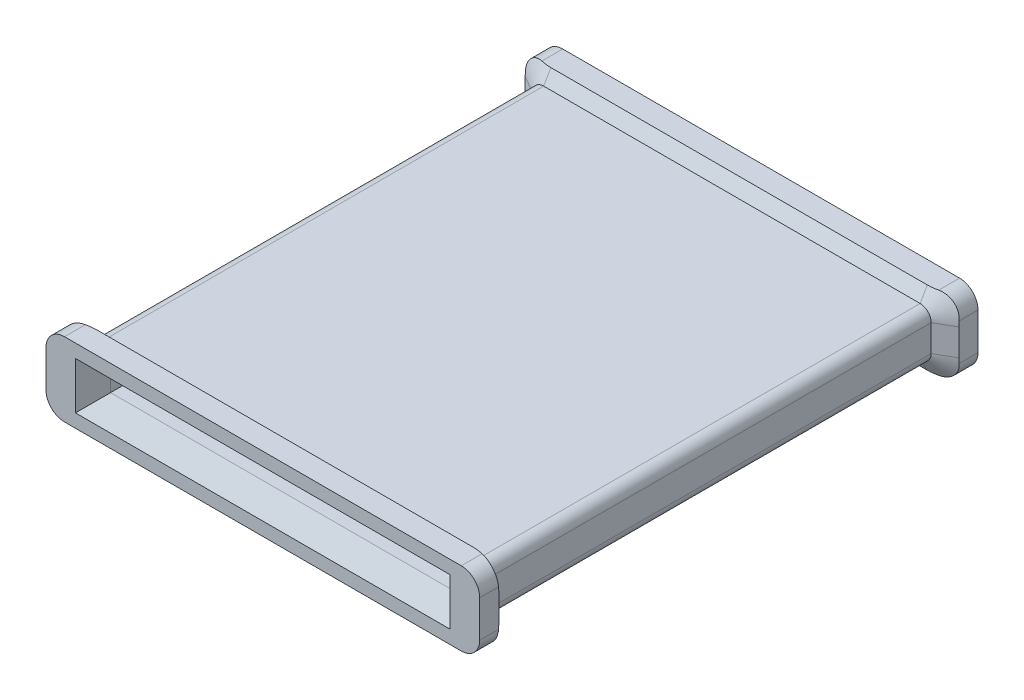
SolidWorks part; units mm, degrees
material "ABS"
ref_plane "Front Plane" through (0, 0, 0) normal (0, 0, 1) x (1, 0, 0)
ref_plane "Top Plane" through (0, 0, 0) normal (0, 1, 0) x (1, 0, 0)
ref_plane "Right Plane" through (0, 0, 0) normal (1, 0, 0) x (0, 0, -1)
sketch "Sketch1" plane through (0, 0, 0) normal (0, 0, 1) x (1, 0, 0)
  line L0 (0, 8) -> (47, 8)
  line L3 (47, 8) -> (47, 0)
  line L4 (47, 0) -> (0, 0)
  line L5 (0, 0) -> (0, 8)
  line L9 (3.5, 6.25) -> (43.5, 6.25)
  line L10 (3.5, 6.25) -> (3.5, 1.75)
  line L11 (3.5, 1.75) -> (43.5, 1.75)
  line L12 (43.5, 6.25) -> (43.5, 1.75)
  dimension "D1" = 1.75
  dimension "D2" = 40
  dimension "D4" = 4.5
  dimension "D5" = 1.75
  dimension "D7" = 3.5
  dimension "D8" = 3.5
extrude "Boss-Extrude1" add sketch "Sketch1" along normal blind 54
sketch "Sketch2" plane through (0, 0, 54) normal (0, 0, 1) x (1, 0, 0)
  line L1 (3.1, 6.65) -> (43.9, 6.65)
  line L2 (1.9, 5.45) -> (1.9, 2.55)
  line L3 (3.1, 1.35) -> (43.9, 1.35)
  line L4 (45.1, 5.45) -> (45.1, 2.55)
  line L5 (3.5, 1.75) -> (43.5, 1.75) construction
  line L6 (43.5, 6.25) -> (3.5, 6.25) construction
  line L8 (3.5, 6.25) -> (3.5, 1.75) construction
  line L9 (43.5, 1.75) -> (43.5, 6.25) construction
  arc A0 (1.9, 2.55) -> (3.1, 1.35) centre (3.1, 2.55) ccw
  arc A1 (43.9, 1.35) -> (45.1, 2.55) centre (43.9, 2.55) ccw
  arc A2 (43.9, 6.65) -> (45.1, 5.45) centre (43.9, 5.45) cw
  arc A3 (3.1, 6.65) -> (1.9, 5.45) centre (3.1, 5.45) ccw
  dimension "D1" = 1.2
  dimension "D2" = 0.4
  dimension "D3" = 1.6
  dimension "D4" = 1.6
  dimension "D5" = 0.4
extrude "Cut-Extrude1" cut sketch "Sketch2" against normal offset from surface (50 mm away) 2 from offset 2 flip side to cut up to face at (23.5, 4, 0) offset against normal yes
fillet "Fillet1" radius 2 8 edges at (47, 8, 53) (47, 0, 53) (47, 0, 1) (47, 8, 1) (0, 0, 1) (0, 8, 1) (0, 0, 53) (0, 8, 53)
chamfer "Chamfer4" distance 1.17 angle 60 16 edges at (1.9, 4, 52) (2.2515, 1.7015, 52) (2.2515, 6.2985, 52) (23.5, 1.35, 52) (23.5, 6.65, 52) (44.7485, 1.7015, 52) (44.7485, 6.2985, 52) (45.1, 4, 52) (1.9, 4, 2) (2.2515, 1.7015, 2) (2.2515, 6.2985, 2) (23.5, 1.35, 2) (23.5, 6.65, 2) (44.7485, 1.7015, 2) (44.7485, 6.2985, 2) (45.1, 4, 2) first distance on face at (1.9, 4, 27) first distance on face at (2.3757, 1.8257, 27) first distance on face at (2.3757, 6.1743, 27) first distance on face at (23.5, 1.35, 27) first distance on face at (23.5, 6.65, 27) first distance on face at (44.6243, 1.8257, 27) first distance on face at (44.6243, 6.1743, 27) first distance on face at (45.1, 4, 27)
chamfer "Chamfer5" distance 3.5 angle 5 8 edges at (43.5, 4, 54) (23.5, 1.75, 54) (3.5, 4, 54) (23.5, 6.25, 54) (43.5, 4, 0) (23.5, 1.75, 0) (3.5, 4, 0) (23.5, 6.25, 0) first distance on face at (43.5, 4, 27) first distance on face at (23.5, 1.75, 27) first distance on face at (3.5, 4, 27) first distance on face at (23.5, 6.25, 27)
